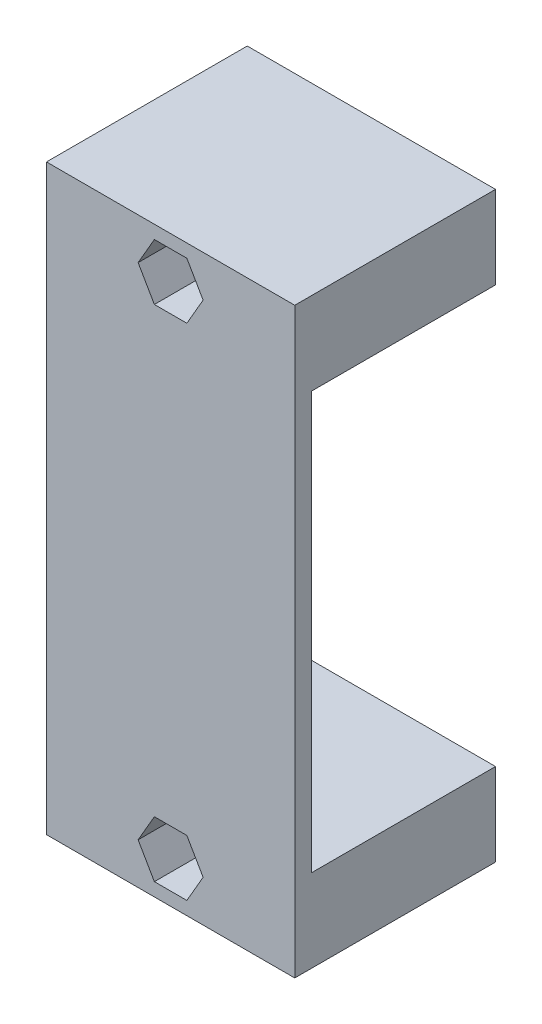
SolidWorks part; units mm, degrees
material "ABS"
ref_plane "Front Plane" through (0, 0, 0) normal (0, 0, 1) x (1, 0, 0)
ref_plane "Top Plane" through (0, 0, 0) normal (0, 1, 0) x (1, 0, 0)
ref_plane "Right Plane" through (0, 0, 0) normal (1, 0, 0) x (0, 0, -1)
sketch "Sketch2" plane through (0, 0, 0) normal (0, 0, 1) x (1, 0, 0)
  line L0 (69, -22) -> (-75.5, -22) construction
  line L1 (-37.5, -32) -> (-7.5, -32)
  line L2 (-37.5, -32) -> (-37.5, 38.4)
  line L3 (-37.5, 38.4) -> (-7.5, 38.4)
  line L4 (-7.5, -32) -> (-7.5, 38.4)
  line L5 (-37.5, -32) -> (-7.5, 38.4) construction
  line L6 (-37.5, 38.4) -> (-7.5, -32) construction
  line L7 (-75.5, 28.4) -> (69, 28.4) construction
  line L8 (-75.5, -22) -> (-75.5, 28.4) construction
  line L9 (-37.5, -22) -> (-7.5, -22) construction
  line L10 (-7.5, -22) -> (-7.5, 28.4) construction
  line L11 (-7.5, 28.4) -> (-37.5, 28.4) construction
  line L12 (-22.5, -32) -> (-22.5, -22) construction
  line L14 (-22.5, 28.4) -> (-22.5, 38.4) construction
  circle A0 centre (-22.5, -27) radius 2
  circle A1 centre (-22.5, 33.4) radius 2
  point P4 (-22.5, 3.2)
  line M7 (69, 28.4) -> (-75.5, 28.4)
  line M9 (-75.5, -22) -> (69, -22)
  dimension "D5" = 4
  dimension "D6" = 4
  dimension "D1" = 10
  dimension "D2" = 10
  dimension "D3" = 38
  dimension "D4" = 30
extrude "Boss-Extrude1" add sketch "Sketch2" along normal blind 2
extrude "Boss-Extrude2" add sketch "Sketch2<2>" against normal up to surface (22.26 mm away) contours L1 L4 L2 A0 M9 | L4 L3 L2 A1 M7 region at (-37.1838, -27, 0) region at (-37.1838, 33.4, 0)
sketch "Sketch2<2>" plane through (0, 0, 0) normal (0, 0, 1) x (1, 0, 0) same geometry as "Sketch2"
sketch "Sketch3" plane through (0, 0, 2) normal (0, 0, 1) x (1, 0, 0)
  line L1 (-24.463, 30) -> (-20.537, 30)
  line L2 (-20.537, 30) -> (-18.574, 33.4)
  line L3 (-18.574, 33.4) -> (-20.537, 36.8)
  line L4 (-20.537, 36.8) -> (-24.463, 36.8)
  line L5 (-24.463, 36.8) -> (-26.426, 33.4)
  line L6 (-26.426, 33.4) -> (-24.463, 30)
  line L7 (-20.537, -30.4) -> (-18.574, -27)
  line L8 (-18.574, -27) -> (-20.537, -23.6)
  line L9 (-20.537, -23.6) -> (-24.463, -23.6)
  line L10 (-24.463, -23.6) -> (-26.426, -27)
  line L11 (-26.426, -27) -> (-24.463, -30.4)
  line L12 (-24.463, -30.4) -> (-20.537, -30.4)
  circle A0 centre (-22.5, 33.4) radius 3.4 construction
  circle A1 centre (-22.5, -27) radius 3.4 construction
  dimension "D1" = 6.8
  dimension "D2" = 6.8
extrude "Cut-Extrude1" cut sketch "Sketch3" against normal blind 14
